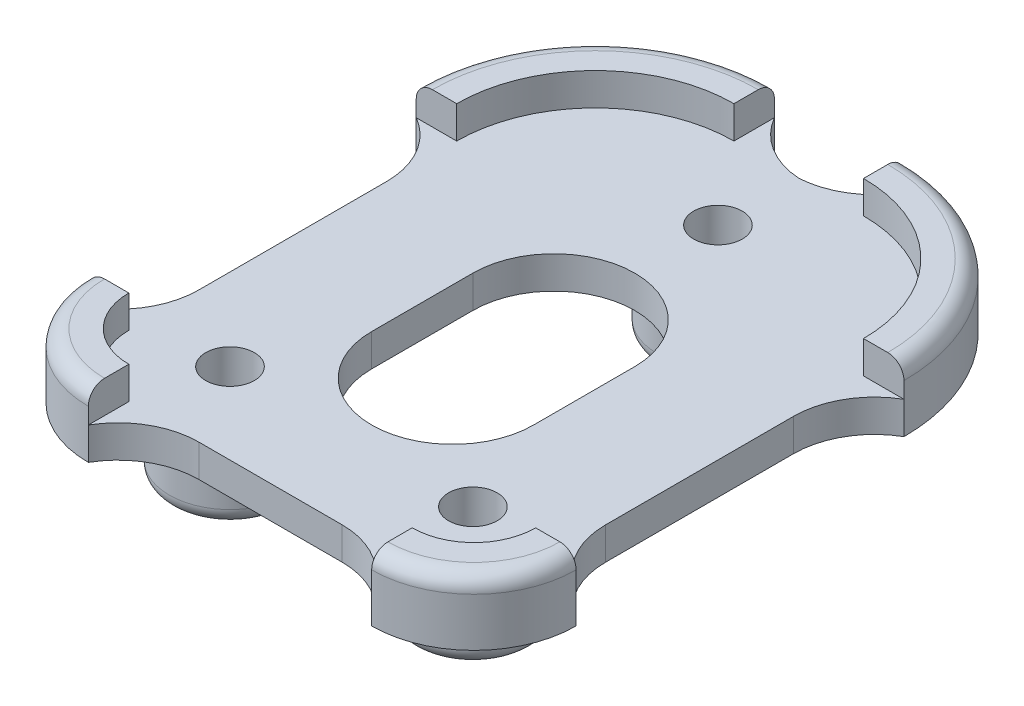
SolidWorks part; units mm, degrees
ref_plane "Alzado" through (0, 0, 0) normal (0, 0, 1) x (1, 0, 0)
ref_plane "Planta" through (0, 0, 0) normal (0, 1, 0) x (1, 0, 0)
ref_plane "Vista lateral" through (0, 0, 0) normal (1, 0, 0) x (0, 0, -1)
sketch "Croquis1" plane through (0, 0, 0) normal (0, 1, 0) x (1, 0, 0)
  line L0 (17.5, 0) -> (-17.5, 0) construction
  line L1 (25, 7.5) -> (25, 48) construction
  line L2 (8, 65) -> (-8, 65) construction
  line L3 (0, -55) -> (0, 55) construction
  line L4 (-25, 7.5) -> (-25, 48) construction
  line L5 (17.5, -0.125) -> (-17.5, -0.125)
  line L6 (-25.125, 7.5) -> (-25.125, 48)
  line L7 (8, 65.125) -> (-8, 65.125)
  line L8 (25.125, 7.5) -> (25.125, 48)
  line L9 (-8, 70.125) -> (-8, 65.125)
  line L10 (-30.125, 48) -> (-25, 48)
  line L11 (-30.125, 7.5) -> (-25.125, 7.5)
  line L12 (-17.5, 0) -> (-17.5, -5.125)
  line L13 (17.5, -5.125) -> (17.5, -0.125)
  line L14 (25, 7.5) -> (30.125, 7.5)
  line L15 (8, 70.125) -> (8, 65.125)
  line L16 (30.125, 48) -> (25, 48)
  line L17 (0, 22.375) -> (0, 34.875) construction
  line L18 (-10, 22.375) -> (-10, 34.875)
  line L19 (10, 22.375) -> (10, 34.875)
  arc A0 (25, 48) -> (8, 65) centre (8, 48) ccw construction
  arc A1 (17.5, 0) -> (25, 7.5) centre (17.5, 7.5) ccw construction
  arc A2 (-17.5, 0) -> (-25, 7.5) centre (-17.5, 7.5) cw construction
  arc A3 (-25, 48) -> (-8, 65) centre (-8, 48) cw construction
  arc A4 (-17.5, -0.125) -> (-25.125, 7.5) centre (-17.5, 7.5) cw
  arc A5 (-25.125, 48) -> (-8, 65.125) centre (-8, 48) cw
  arc A6 (25.125, 48) -> (8, 65.125) centre (8, 48) ccw
  arc A7 (17.5, -0.125) -> (25.125, 7.5) centre (17.5, 7.5) ccw
  arc A8 (30.125, 48) -> (8, 70.125) centre (8, 48) ccw
  arc A9 (17.5, -5.125) -> (30.125, 7.5) centre (17.5, 7.5) ccw
  arc A10 (-30.125, 48) -> (-8, 70.125) centre (-8, 48) cw
  arc A11 (-17.5, -5.125) -> (-30.125, 7.5) centre (-17.5, 7.5) cw
  arc A12 (-10, 22.375) -> (10, 22.375) centre (0, 22.375) ccw
  arc A13 (10, 34.875) -> (-10, 34.875) centre (0, 34.875) ccw
  point P7 (0, 0)
  point P18 (0, 65)
  point P43 (0, 28.625)
  dimension "D2" = 17
  dimension "D4" = 7.5
  dimension "D9" = 10
  dimension "D10" = 22.5
  dimension "D1" = 8
  dimension "D3" = 40.5
  dimension "D5" = 0.125
  dimension "D8" = 12.5
  dimension "D6" = 5
  dimension "D7" = 5
extrude "Saliente-Extruir1" add sketch "Croquis1" along normal blind 4 contours L5 A7 L8 A6 L7 A5 L6 A4 | A11 L12 A4 L11 | L13 A9 L14 A7 | L16 A8 L15 A6 | A10 L10 A5 L9 region at (24.0768, 0, -0.9232) region at (0, 0, -0.6986) region at (-24.0768, 0, -0.9232) region at (20.5612, 0, -60.5612) region at (-20.5612, 0, -60.5612)
extrude "Saliente-Extruir2" add sketch "Croquis1<3>" along normal blind 4 from surface contours A10 L10 A5 L9 | A11 L12 A4 L11 | L13 A9 L14 A7 | L16 A8 L15 A6 region at (24.0768, 0, -0.9232) region at (-24.0768, 0, -0.9232) region at (20.5612, 0, -60.5612) region at (-20.5612, 0, -60.5612) starting at face at (0, 4, -30.3709)
sketch "Croquis1<3>" plane through (0, 0, 0) normal (0, 1, 0) x (1, 0, 0) same geometry as "Croquis1"
fillet "Redondeo1" radius 10 8 edges at (8, 2, -65.125) (-8, 2, -65.125) (-17.5, 2, 0.125) (17.5, 2, 0.125) (25.125, 2, -48) (25.125, 2, -7.5) (-25.125, 2, -7.5) (-25.125, 2, -48)
fillet "Redondeo3" radius 2 4 edges at (26.4272, 8, 1.4272) (23.6447, 8, -63.6447) (-23.6447, 8, -63.6447) (-26.4272, 8, 1.4272)
sketch "Croquis2" plane through (0, 0, 0) normal (0, -1, 0) x (1, 0, 0)
  line L0 (8.8397, 0.125) -> (-8.8397, 0.125) construction
  circle A0 centre (0, -55.1468) radius 7.5
  circle A2 centre (-15, -9.875) radius 7.5
  circle A3 centre (-15, -9.875) radius 3
  circle A4 centre (0, -55.1468) radius 3
  dimension "D3" = 10
  dimension "D4" = 15
  dimension "D5" = 15
  dimension "D6" = 6
  dimension "D1" = 15
  dimension "D2" = 10
extrude "Saliente-Extruir3" add sketch "Croquis2" along normal blind 8 contours A2 region at (-22.2879, 0, -9.875)
extrude "Saliente-Extruir4" add sketch "Croquis2<3>" along normal blind 8 contours A0 region at (-7.2879, 0, -55.1468)
sketch "Croquis2<3>" plane through (0, 0, 0) normal (0, -1, 0) x (1, 0, 0) same geometry as "Croquis2"
ref_plane "Plano1" through (0, 0, -9.875) normal (0, 0, 1) x (1, 0, 0)
sketch "Croquis3" plane through (0, 0, -9.875) normal (0, 0, 1) x (1, 0, 0)
  line L1 (-9.875, -5.5) -> (-20.125, -5.5)
  line L3 (-22.5, 0) -> (-22.5, -8) construction
  line L5 (-22.5, -8) -> (-7.5, -8) construction
  arc A1 (-20.125, -5.5) -> (-9.875, -5.5) centre (-15, -5.5) ccw
  dimension "D2" = 5.125
  dimension "D1" = 7.5
  dimension "D3" = 2.5
ref_plane "Plano2" through (0, 0, -55.1468) normal (0, 0, 1) x (1, 0, 0)
sketch "Croquis4" plane through (0, 0, -55.1468) normal (0, 0, 1) x (1, 0, 0)
  line L0 (5.125, -5.5) -> (-5.125, -5.5)
  line L1 (-9.875, -5.5) -> (-20.125, -5.5) construction
  arc A0 (-5.125, -5.5) -> (5.125, -5.5) centre (0, -5.5) ccw
  arc A1 (-20.125, -5.5) -> (-9.875, -5.5) centre (-15, -5.5) ccw construction
revolve "Cortar-Revolución1" cut sketch "Croquis3" angle 360 about L1
revolve "Cortar-Revolución2" cut sketch "Croquis4" angle 360 about L0
fillet "Redondeo4" radius 2 2 edges at (-15, 0, -2.375) (-15, -8, -17.375)
fillet "Redondeo5" radius 2 2 edges at (0, 0, -47.6468) (0, -8, -62.6468)
mirror "Simetría1" about plane through (0, 0, 0) normal (1, 0, 0) of "Redondeo4", "Cortar-Revolución1", "Saliente-Extruir3"
extrude "Cortar-Extruir1" cut sketch "Croquis2<4>" against normal through all contours A4 | A3 region at (-15, 0, -9.875) region at (0, 0, -55.1468)
sketch "Croquis2<4>" plane through (0, 0, 0) normal (0, -1, 0) x (1, 0, 0) same geometry as "Croquis2"
sketch "Croquis5" plane through (0, 0, 0) normal (0, -1, 0) x (1, 0, 0)
  circle A1 centre (15, -9.875) radius 3
  circle A2 centre (15, -9.875) radius 3
  dimension "D1" = 0
extrude "Cortar-Extruir2" cut sketch "Croquis5" against normal through all
